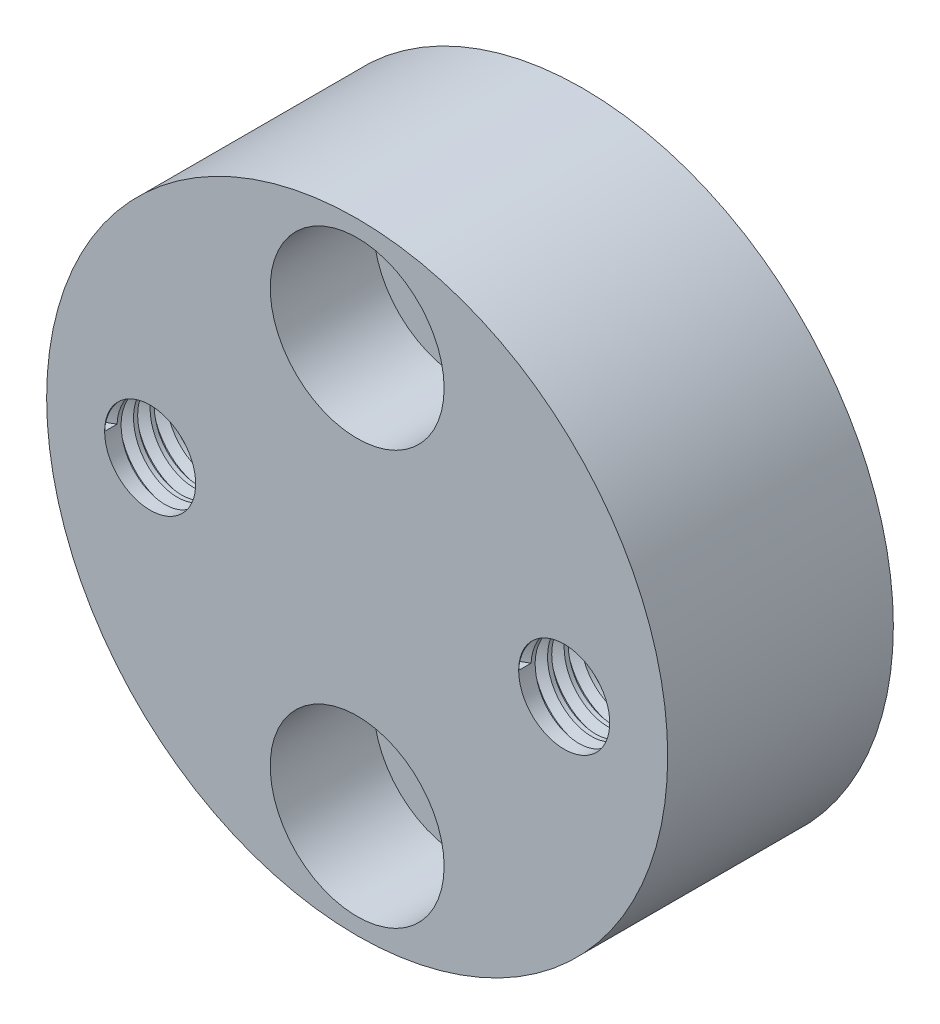
SolidWorks part; units mm, degrees
ref_plane "Ebene vorne" through (0, 0, 0) normal (0, 0, 1) x (1, 0, 0)
ref_plane "Ebene oben" through (0, 0, 0) normal (0, 1, 0) x (1, 0, 0)
ref_plane "Ebene rechts" through (0, 0, 0) normal (1, 0, 0) x (0, 0, -1)
sketch "Skizze1" plane through (0, 0, 0) normal (0, 0, 1) x (1, 0, 0)
  circle A0 centre (0, 0) radius 15
  dimension "D1" = 30
extrude "Aufsatz-Linear austragen1" add sketch "Skizze1" along normal blind 10.9
sketch "Skizze2" plane through (0, 0, 10.9) normal (0, 0, 1) x (1, 0, 0)
  circle A0 centre (0, 10) radius 2.5
  circle A1 centre (10, 0) radius 2.2
  circle A2 centre (0, -10) radius 2.5
  circle A3 centre (-10, 0) radius 2.2
  dimension "D1" = 4.4
  dimension "D2" = 5
  dimension "D3" = 4.4
  dimension "D4" = 5
  dimension "D5" = 10
  dimension "D6" = 10
  dimension "D7" = 10
  dimension "D8" = 10
extrude "Schnitt-Linear austragen1" cut sketch "Skizze2" against normal blind 33
sketch "Skizze3" plane through (0, 0, 10.9) normal (0, 0, 1) x (1, 0, 0)
  circle A0 centre (0, 10) radius 4.2
  circle A1 centre (0, -10) radius 4.2
  dimension "D1" = 8.4
  dimension "D2" = 8.4
extrude "Schnitt-Linear austragen2" cut sketch "Skizze3" against normal blind 5
thread "Gewinde1" pitch 0.8 start angle 0, offset 0, length 20, pitch 0.8, diameter 4.4
ref_plane "Ebene1" through (-12.2, 0, 10.9) normal (0, -1, 0) x (-1, 0, 0)
sketch "Gewindeprofil1" plane through (-12.2, 0, 10.9) normal (0, -1, 0) x (-1, 0, 0)
  line L0 (0, 0) -> (0, 0.8) construction
  line L1 (0, 0) -> (0.433, 0.25)
  line L2 (0.433, 0.25) -> (0.433, 0.35)
  line L3 (0.433, 0.35) -> (0, 0.6)
  line L4 (0.433, 0.3) -> (0, 0.3) construction
  line L11 (0, 0) -> (0, 0.6)
  point P2 (0, 0)
  dimension "Pitch" = 0.8
  dimension "Profile_Angle" = 60
  dimension "Profile_Land" = 0.1
  dimension "Profile_Height" = 0.433
thread "Gewinde2" pitch 0.8 profile "Gewindeprofil2" start angle 0, offset 0, length 20, pitch 0.8, diameter 4.4
ref_plane "Ebene2" through (7.8, 0, 10.9) normal (0, -1, 0) x (-1, 0, 0)
sketch "Gewindeprofil2" plane through (7.8, 0, 10.9) normal (0, -1, 0) x (-1, 0, 0)
  line L0 (0, 0) -> (0, 0.8) construction
  line L1 (0, 0) -> (0.433, 0.25)
  line L2 (0.433, 0.25) -> (0.433, 0.35)
  line L3 (0.433, 0.35) -> (0, 0.6)
  line L4 (0.433, 0.3) -> (0, 0.3) construction
  line L11 (0, 0) -> (0, 0.6)
  point P2 (0, 0)
  dimension "Pitch" = 0.8
  dimension "Profile_Angle" = 60
  dimension "Profile_Land" = 0.1
  dimension "Profile_Height" = 0.433
